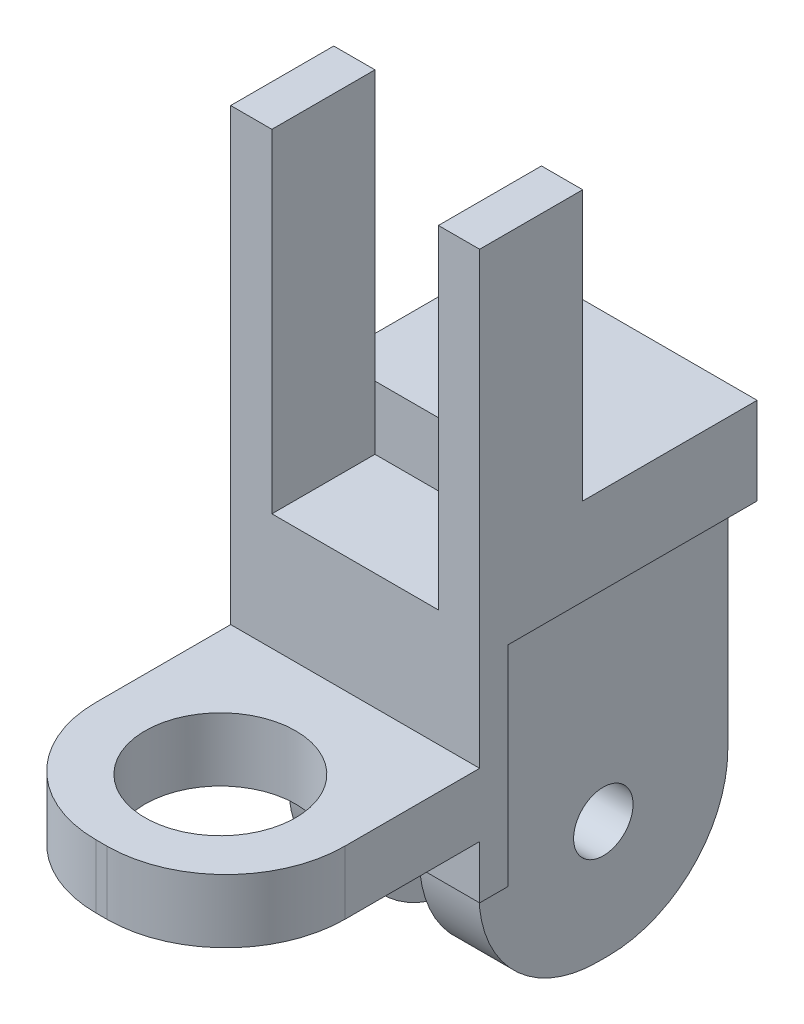
SolidWorks part; units mm, degrees
ref_plane "Front Plane" through (0, 0, 0) normal (0, 0, 1) x (1, 0, 0)
ref_plane "Top Plane" through (0, 0, 0) normal (0, 1, 0) x (1, 0, 0)
ref_plane "Right Plane" through (0, 0, 0) normal (1, 0, 0) x (0, 0, -1)
sketch "Sketch4" plane through (0, 0, 0) normal (0, 0, 1) x (1, 0, 0)
  line L0 (0, 82.063) -> (0, -112.4411) construction
  line L1 (-144.2959, 0) -> (145.5617, 0) construction
  line L2 (-12.7, 12.7) -> (-12.7, -12.7)
  line L3 (-15.7, 15.7) -> (15.7, 15.7)
  line L4 (-15.7, 15.7) -> (-15.7, -15.7)
  line L5 (-15.7, -15.7) -> (15.7, -15.7)
  line L6 (15.7, 15.7) -> (15.7, -15.7)
  line L7 (-12.7, -12.7) -> (12.7, -12.7)
  line L8 (12.7, 12.7) -> (12.7, -12.7)
  line L9 (-12.7, 12.7) -> (12.7, 12.7)
  dimension "D2" = 12.7
  dimension "D3" = 12.7
  dimension "D4" = 12.7
  dimension "D5" = 12.7
  dimension "D1" = 3
extrude "Boss-Extrude3" add sketch "Sketch4" along normal blind 30
sketch "Sketch5" plane through (0, 0, 30) normal (0, 0, 1) x (1, 0, 0)
  line L0 (-15.7, 15.7) -> (15.7, 15.7)
  line L1 (15.7, 15.7) -> (15.7, -15.7)
  line L2 (15.7, -15.7) -> (-15.7, -15.7)
  line L3 (-15.7, -15.7) -> (-15.7, 15.7)
extrude "Boss-Extrude4" add sketch "Sketch5" along normal blind 5
sketch "Sketch6" plane through (0, 0, 35) normal (0, 0, 1) x (1, 0, 0)
  line L0 (-14.6567, 0) -> (15.7, 0) construction
  line L1 (15.7, -15.7) -> (15.7, 15.7) construction
  line L2 (-15.7, 4) -> (15.7, 4)
  line L3 (-15.7, 15.7) -> (-15.7, -15.7) construction
  line L4 (15.7, 4) -> (15.7, -4)
  line L5 (15.7, -4) -> (-15.7, -4)
  line L6 (-15.7, -4) -> (-15.7, 4)
  dimension "D1" = 4
  dimension "D2" = 4
extrude "Boss-Extrude5" add sketch "Sketch6" along normal blind 5
sketch "Sketch7" plane through (0, -4, 0) normal (0, -1, 0) x (1, 0, 0)
  line L0 (-15.7, 40) -> (-15.7, 52)
  line L1 (-0.7, 67) -> (0.7, 67)
  line L2 (15.7, 52) -> (15.7, 40)
  line L3 (-15.7, 40) -> (15.7, 40) construction
  line L4 (15.7, 40) -> (-15.7, 40)
  line L5 (0, 0) -> (0, 92.3619) construction
  arc A0 (0.7, 67) -> (15.7, 52) centre (0.7, 52) cw
  arc A1 (-15.7, 52) -> (-0.7, 67) centre (-0.7, 52) cw
  point P9 (15.7, 67)
  point P12 (-15.7, 67)
  dimension "D3" = 15
  dimension "D1" = 27
  dimension "D2" = 31.4
extrude "Boss-Extrude6" add sketch "Sketch7" against normal blind 8
sketch "Sketch8" plane through (0, -4, 0) normal (0, -1, 0) x (1, 0, 0)
  line L0 (0, 67.4318) -> (0, -5.9603) construction
  line L1 (0.7, 67) -> (-0.7, 67) construction
  circle A0 centre (0, 52) radius 9.5
  dimension "D1" = 15
extrude "Boss-Extrude7" add sketch "Sketch8" along normal blind 8
mirror "Mirror1" about plane through (0, 0, 0) normal (0, 1, 0) of "Boss-Extrude7"
sketch "Sketch9" plane through (0, 15.7, 0) normal (0, 1, 0) x (1, 0, 0)
  line L1 (-15.7, -32) -> (15.7, -32)
  line L2 (-15.7, -35) -> (-15.7, 0) construction
  line L3 (15.7, -35) -> (15.7, 0) construction
  line L4 (0, 15.8647) -> (0, -78.6922) construction
  line L5 (0, -52) -> (31.7707, -52) construction
  line L6 (31.7707, -52) -> (-30.9902, -52) construction
  line L7 (-15.7, -32) -> (-15.7, -22)
  line L8 (-15.7, -22) -> (15.7, -22)
  line L9 (15.7, -22) -> (15.7, -32)
  dimension "D1" = 20
  dimension "D2" = 10
extrude "Boss-Extrude8" add sketch "Sketch9" along normal blind 5
sketch "Sketch10" plane through (0, 15.7, 0) normal (0, 1, 0) x (1, 0, 0)
  line L0 (-15.7, -22) -> (-15.7, -12)
  line L1 (-15.7, -22) -> (-15.7, 0) construction
  line L2 (-15.7, -12) -> (15.7, -12)
  line L3 (15.7, -22) -> (15.7, 0) construction
  line L4 (15.7, -12) -> (15.7, -22)
  line L5 (15.7, -22) -> (-15.7, -22)
  dimension "D1" = 10
extrude "Boss-Extrude9" add sketch "Sketch10" along normal blind 11
sketch "Sketch11" plane through (0, 20.7, 0) normal (0, 1, 0) x (1, 0, 0)
  line L0 (-15.7, -22) -> (-10.5, -22)
  line L1 (15.7, -22) -> (-15.7, -22) construction
  line L2 (-10.5, -22) -> (-10.5, -32)
  line L3 (-15.7, -32) -> (15.7, -32) construction
  line L4 (-10.5, -32) -> (-15.7, -32)
  line L5 (-15.7, -32) -> (-15.7, -22)
  line L6 (10.5, -22) -> (10.5, -32)
  line L7 (-15.7, -22) -> (15.7, -22) construction
  line L8 (-15.7, -32) -> (15.7, -32) construction
  line L9 (10.5, -32) -> (15.7, -32)
  line L10 (15.7, -32) -> (15.7, -22)
  line L11 (15.7, -32) -> (15.7, -22) construction
  line L12 (15.7, -22) -> (10.5, -22)
  dimension "D1" = 5.2
  dimension "D2" = 5.2
extrude "Boss-Extrude10" add sketch "Sketch11" along normal blind 40
sketch "Sketch12" plane through (0, 0, 32) normal (0, 0, 1) x (1, 0, 0)
  line L0 (-15.7, 60.7) -> (-10.5, 60.7)
  line L1 (-10.5, 60.7) -> (-10.5, 20.7)
  line L2 (-10.5, 20.7) -> (10.5, 20.7)
  line L3 (10.5, 20.7) -> (10.5, 60.7)
  line L4 (10.5, 60.7) -> (15.7, 60.7)
  line L5 (15.7, 60.7) -> (15.7, 15.7)
  line L6 (15.7, 15.7) -> (-15.7, 15.7)
  line L7 (-15.7, 15.7) -> (-15.7, 60.7)
  dimension "D1" = 5.2
  dimension "D2" = 5.2
  dimension "D3" = 21
extrude "Boss-Extrude11" add sketch "Sketch12" along normal blind 3
sketch "Sketch13" plane through (-15.7, 0, 0) normal (-1, 0, 0) x (0, 0, 1)
  line L5 (0, 15.7) -> (31.4, 15.7)
  line L6 (31.4, 15.7) -> (31.4, -15.7)
  line L7 (35, -15.7) -> (0, -15.7) construction
  line L8 (31.4, -15.7) -> (0, -15.7)
  line L9 (0, -15.7) -> (0, 15.7)
  dimension "D1" = 31.4
extrude "Cut-Extrude1" cut sketch "Sketch13" against normal blind 31.4
sketch "Sketch15" plane through (0, 0, 12) normal (0, 0, -1) x (-1, 0, 0)
  line L0 (-15.7, 26.7) -> (15.7, 26.7)
  line L1 (15.7, 26.7) -> (15.7, 15.7)
  line L2 (15.7, 15.7) -> (-15.7, 15.7)
  line L3 (-15.7, 15.7) -> (-15.7, 26.7)
extrude "Boss-Extrude12" add sketch "Sketch15" along normal blind 12
sketch "Sketch17" plane through (0, 15.7, 0) normal (0, -1, 0) x (1, 0, 0)
  line L0 (0, 70.9174) -> (0, -6.6676) construction
  line L1 (-12, 31.4) -> (-12, 0)
  line L2 (15.7, 31.4) -> (-15.7, 31.4) construction
  line L3 (15.7, 0) -> (-15.7, 0) construction
  line L4 (-12, 0) -> (-4.5, 0)
  line L5 (-4.5, 0) -> (-4.5, 31.4)
  line L6 (15.7, 31.4) -> (-15.7, 31.4) construction
  line L7 (-4.5, 31.4) -> (-12, 31.4)
  line L8 (-15.7, 31.4) -> (-15.7, 0) construction
  dimension "D1" = 7.5
  dimension "D2" = 3.7
  dimension "D3" = 4.5
extrude "Boss-Extrude13" add sketch "Sketch17" along normal blind 10
sketch "Sketch18" plane through (-12, 0, 0) normal (-1, 0, 0) x (0, 0, 1)
  line L1 (31.4, 5.7) -> (0, 5.7)
  line L4 (0, 5.7) -> (0, -13.3)
  line L5 (15, -28.3) -> (16.4, -28.3)
  line L6 (31.4, -13.3) -> (31.4, 5.7)
  arc A3 (16.4, -28.3) -> (31.4, -13.3) centre (16.4, -13.3) ccw
  arc A4 (0, -13.3) -> (15, -28.3) centre (15, -13.3) ccw
  circle A5 centre (15.7, -13.3) radius 3.75
  point P12 (0, -28.3)
  dimension "D1" = 34
  dimension "D2" = 15
  dimension "D3" = 15
  dimension "D4" = 15.7
extrude "Boss-Extrude14" add sketch "Sketch18" against normal blind 7.5
mirror "Mirror3" about plane through (0, 0, 0) normal (1, 0, 0) of "Boss-Extrude13", "Boss-Extrude14"
sketch "Sketch19" plane through (15.7, 0, 0) normal (1, 0, 0) x (0, 0, -1)
  line L0 (-31.4, -10.7) -> (-35, -10.7)
  line L3 (-31.4, -15.7) -> (-31.4, 15.7) construction
  line L4 (-35, -15.7) -> (-35, -4) construction
  line L5 (-35, -10.7) -> (-35, -15.7)
  line L6 (-35, -15.7) -> (-31.4, -15.7)
  line L7 (-31.4, -15.7) -> (-31.4, -10.7)
  dimension "D1" = 5
extrude "Cut-Extrude2" cut sketch "Sketch19" against normal blind 31.4
extrude "Cut-Extrude3" cut sketch "Sketch8<2>" against normal blind 24 from offset 8
sketch "Sketch8<2>" plane through (0, -4, 0) normal (0, -1, 0) x (1, 0, 0) same geometry as "Sketch8"
sketch "Sketch20" plane through (0, -10.7, 0) normal (0, -1, 0) x (1, 0, 0)
  line L0 (-4.5, 31.4) -> (-4.5, 32.4)
  line L1 (-4.5, 32.4) -> (4.5, 32.4)
  line L2 (4.5, 32.4) -> (4.5, 31.4)
  line L3 (4.5, 31.4) -> (-4.5, 31.4)
  dimension "D1" = 1
extrude "Cut-Extrude4" cut sketch "Sketch20" against normal blind 26.4
sketch "Sketch21" plane through (0, 20.7, 0) normal (0, 1, 0) x (1, 0, 0)
  line L0 (10.5, -22) -> (10.5, -35)
  line L1 (15.7, -35) -> (-15.7, -35) construction
  line L2 (15.7, -35) -> (10.5, -35) construction
  line L3 (10.5, -35) -> (-10.5, -35)
  line L4 (10.5, -35) -> (-10.5, -35) construction
  line L5 (-10.5, -35) -> (-10.5, -22)
  line L6 (-10.5, -22) -> (10.5, -22)
extrude "Cut-Extrude5" cut sketch "Sketch21" against normal blind 2
